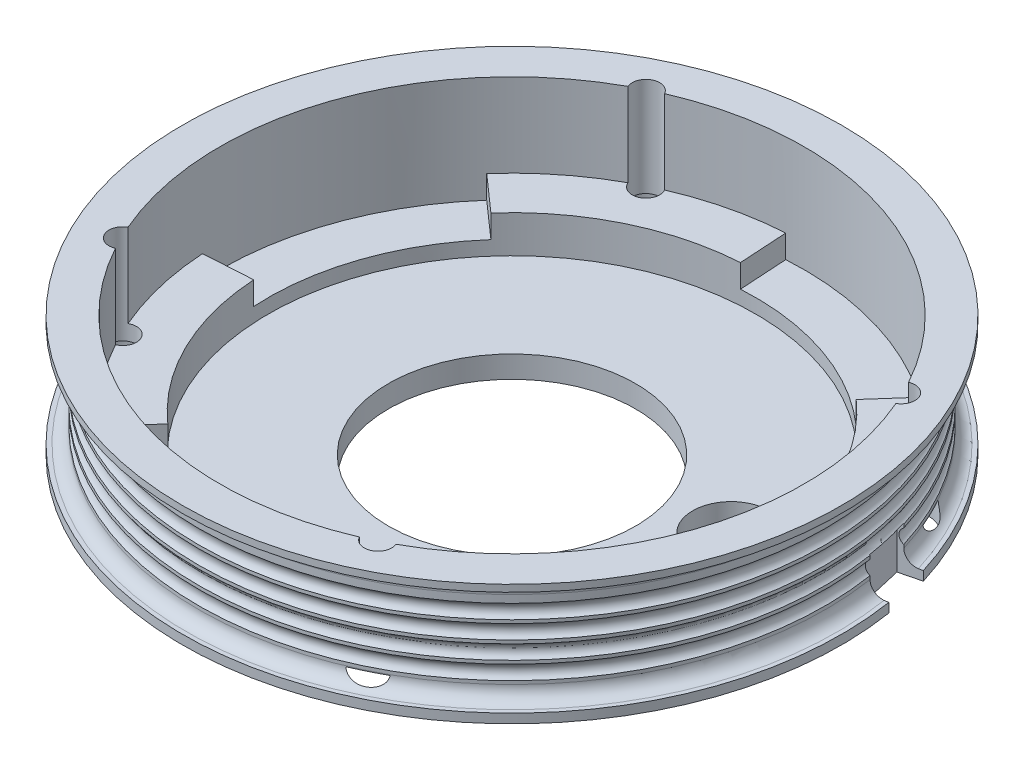
SolidWorks part; units mm, degrees
ref_plane "Front Plane" through (0, 0, 0) normal (0, 0, 1) x (1, 0, 0)
ref_plane "Top Plane" through (0, 0, 0) normal (0, 1, 0) x (1, 0, 0)
ref_plane "Right Plane" through (0, 0, 0) normal (1, 0, 0) x (0, 0, -1)
sketch "Sketch1" plane through (0, 0, 0) normal (0, 1, 0) x (1, 0, 0)
  circle A1 centre (0, 0) radius 23
extrude "Boss-Extrude1" add sketch "Sketch1" against normal blind 2
sketch "Sketch2" plane through (0, 0, 0) normal (0, 1, 0) x (1, 0, 0)
  circle A0 centre (0, 0) radius 30
  circle A1 centre (0, 0) radius 22.2
extrude "Boss-Extrude2" add sketch "Sketch2" along normal blind 11
sketch "Sketch3" plane through (0, 0, 0) normal (0, 1, 0) x (1, 0, 0)
  circle A0 centre (0, 0) radius 11.25
extrude "Cut-Extrude1" cut sketch "Sketch3" against normal blind 10 contours A0
ref_plane "Plane1" through (0, 11, 0) normal (0, 1, 0) x (1, 0, 0)
ref_plane "Plane2" through (0, -2, 0) normal (0, -1, 0) x (-1, 0, 0)
ref_plane "Plane3" through (0, 0, 0) normal (0, -1, 0) x (-1, 0, 0)
sketch "Sketch6" plane through (0, 0, 0) normal (1, 0, 0) x (0, 0, -1)
  line L0 (29.6174, 10.3701) -> (30.176, 10.3701)
  line L1 (30.176, 10.3701) -> (30.176, 0.8441)
  line L2 (30.176, 5.6071) -> (35.5665, 5.6071) construction
  line L3 (30.176, 0.8441) -> (29.6174, 0.8441)
  line L4 (28.5358, 8.7702) -> (28.5358, 8.4631)
  line L5 (28.5358, 7.1702) -> (28.5358, 6.8631)
  line L6 (28.5358, 5.5702) -> (28.5358, 5.2631)
  line L7 (28.5358, 3.9702) -> (28.5358, 3.6631)
  line L8 (28.5358, 2.3702) -> (28.5358, 2.0631)
  line L9 (28.5358, 9.1511) -> (28.5358, 8.7702)
  arc A0 (28.5358, 9.1511) -> (29.6174, 10.3701) centre (29.7636, 9.1511) cw
  arc A1 (28.5358, 8.4631) -> (28.5358, 7.1702) centre (28.9161, 7.8166) ccw
  arc A2 (28.5358, 6.8631) -> (28.5358, 5.5702) centre (28.9161, 6.2166) ccw
  arc A3 (28.5358, 5.2631) -> (28.5358, 3.9702) centre (28.9161, 4.6166) ccw
  arc A4 (28.5358, 3.6631) -> (28.5358, 2.3702) centre (28.9161, 3.0166) ccw
  arc A5 (28.5358, 2.0631) -> (29.6174, 0.8441) centre (29.7636, 2.0631) ccw
  dimension "D2" = 1.6
  dimension "D3" = 1.6
  dimension "D4" = 1.6
ref_axis "Axis1" through (0, -2, 0) along (0, 1, 0)
sketch "Sketch10" plane through (0, 11, 0) normal (0, 1, 0) x (1, 0, 0)
  line L0 (8.2003, -23.949) -> (8.0956, -20.7964)
  line L1 (8.2003, -23.949) -> (7.2077, -21.0502) construction
  line L2 (8.2003, -23.949) -> (6.3506, -21.3939)
  line L3 (6.1946, -24.5444) -> (6.3506, -21.3939)
  line L5 (6.1946, -24.5444) -> (4.5623, -21.8453)
  line L6 (4.1466, -24.9721) -> (4.5623, -21.8453)
  line L7 (4.1466, -24.9721) -> (2.7427, -22.1474)
  line L8 (2.0703, -25.2292) -> (2.7427, -22.1474)
  line L9 (2.0703, -25.2292) -> (0.9044, -22.2983)
  line L10 (-0.0202, -25.314) -> (0.9044, -22.2983)
  line L11 (-0.0202, -25.314) -> (-0.9401, -22.2968)
  line L12 (-2.1106, -25.2259) -> (-0.9401, -22.2968)
  line L13 (-2.1106, -25.2259) -> (-2.7781, -22.143)
  line L14 (-4.1865, -24.9654) -> (-2.7781, -22.143)
  line L15 (-4.1865, -24.9654) -> (-4.5972, -21.838)
  line L16 (-6.2338, -24.5345) -> (-4.5972, -21.838)
  line L17 (-6.2338, -24.5345) -> (-6.3848, -21.3837)
  line L18 (-8.2386, -23.9359) -> (-6.3848, -21.3837)
  line L19 (-8.2386, -23.9359) -> (-8.1289, -20.7835)
  line L20 (-10.1871, -23.1738) -> (-8.1289, -20.7835)
  line L21 (-10.1871, -23.1738) -> (-9.8174, -20.0412)
  line L22 (-12.0659, -22.2534) -> (-9.8174, -20.0412)
  line L23 (-12.0659, -22.2534) -> (-11.4389, -19.162)
  line L24 (-13.8624, -21.181) -> (-11.4389, -19.162)
  line L25 (-13.8624, -21.181) -> (-12.9822, -18.152)
  line L26 (-15.5642, -19.9639) -> (-12.9822, -18.152)
  line L27 (-15.5642, -19.9639) -> (-14.4368, -17.0179)
  line L28 (-17.1596, -18.6104) -> (-14.4368, -17.0179)
  line L29 (-17.1596, -18.6104) -> (-15.7928, -15.7676)
  line L30 (-18.6378, -17.1298) -> (-15.7928, -15.7676)
  line L31 (-18.6378, -17.1298) -> (-17.041, -14.4096)
  line L32 (-19.9887, -15.5322) -> (-17.041, -14.4096)
  line L33 (-19.9887, -15.5322) -> (-18.1727, -12.9531)
  line L34 (-21.2031, -13.8285) -> (-18.1727, -12.9531)
  line L35 (-21.2031, -13.8285) -> (-19.1803, -11.4082)
  line L36 (-22.2726, -12.0304) -> (-19.1803, -11.4082)
  line L37 (-22.2726, -12.0304) -> (-20.0569, -9.7854)
  line L38 (-23.19, -10.15) -> (-20.0569, -9.7854)
  line L39 (-23.19, -10.15) -> (-20.7964, -8.0956)
  line L40 (-23.949, -8.2003) -> (-20.7964, -8.0956)
  line L41 (-23.949, -8.2003) -> (-21.3939, -6.3506)
  line L42 (-24.5444, -6.1946) -> (-21.3939, -6.3506)
  line L43 (-24.5444, -6.1946) -> (-21.8453, -4.5623)
  line L44 (-24.9721, -4.1466) -> (-21.8453, -4.5623)
  line L45 (-24.9721, -4.1466) -> (-22.1474, -2.7427)
  line L46 (-25.2292, -2.0703) -> (-22.1474, -2.7427)
  line L47 (-25.2292, -2.0703) -> (-22.2983, -0.9044)
  line L48 (-25.314, 0.0202) -> (-22.2983, -0.9044)
  line L49 (-25.314, 0.0202) -> (-22.2968, 0.9401)
  line L50 (-25.2259, 2.1106) -> (-22.2968, 0.9401)
  line L51 (-25.2259, 2.1106) -> (-22.143, 2.7781)
  line L52 (-24.9654, 4.1865) -> (-22.143, 2.7781)
  line L53 (-24.9654, 4.1865) -> (-21.838, 4.5972)
  line L54 (-24.5345, 6.2338) -> (-21.838, 4.5972)
  line L55 (-24.5345, 6.2338) -> (-21.3837, 6.3848)
  line L56 (-23.9359, 8.2386) -> (-21.3837, 6.3848)
  line L57 (-23.9359, 8.2386) -> (-20.7835, 8.1289)
  line L58 (-23.1738, 10.1871) -> (-20.7835, 8.1289)
  line L59 (-23.1738, 10.1871) -> (-20.0412, 9.8174)
  line L60 (-22.2534, 12.0659) -> (-20.0412, 9.8174)
  line L61 (-22.2534, 12.0659) -> (-19.162, 11.4389)
  line L62 (-21.181, 13.8624) -> (-19.162, 11.4389)
  line L63 (-21.181, 13.8624) -> (-18.152, 12.9822)
  line L64 (-19.9639, 15.5642) -> (-18.152, 12.9822)
  line L65 (-19.9639, 15.5642) -> (-17.0179, 14.4368)
  line L66 (-18.6104, 17.1596) -> (-17.0179, 14.4368)
  line L67 (-18.6104, 17.1596) -> (-15.7676, 15.7928)
  line L68 (-17.1298, 18.6378) -> (-15.7676, 15.7928)
  line L69 (-17.1298, 18.6378) -> (-14.4096, 17.041)
  line L70 (-15.5322, 19.9887) -> (-14.4096, 17.041)
  line L71 (-15.5322, 19.9887) -> (-12.9531, 18.1727)
  line L72 (-13.8285, 21.2031) -> (-12.9531, 18.1727)
  line L73 (-13.8285, 21.2031) -> (-11.4082, 19.1803)
  line L74 (-12.0304, 22.2726) -> (-11.4082, 19.1803)
  line L75 (-12.0304, 22.2726) -> (-9.7854, 20.0569)
  line L76 (-10.15, 23.19) -> (-9.7854, 20.0569)
  line L77 (-10.15, 23.19) -> (-8.0956, 20.7964)
  line L78 (-8.2003, 23.949) -> (-8.0956, 20.7964)
  line L79 (-8.2003, 23.949) -> (-6.3506, 21.3939)
  line L80 (-6.1946, 24.5444) -> (-6.3506, 21.3939)
  line L81 (-6.1946, 24.5444) -> (-4.5623, 21.8453)
  line L82 (-4.1466, 24.9721) -> (-4.5623, 21.8453)
  line L83 (-4.1466, 24.9721) -> (-2.7427, 22.1474)
  line L84 (-2.0703, 25.2292) -> (-2.7427, 22.1474)
  line L85 (-2.0703, 25.2292) -> (-0.9044, 22.2983)
  line L86 (0.0202, 25.314) -> (-0.9044, 22.2983)
  line L87 (0.0202, 25.314) -> (0.9401, 22.2968)
  line L88 (2.1106, 25.2259) -> (0.9401, 22.2968)
  line L89 (2.1106, 25.2259) -> (2.7781, 22.143)
  line L90 (4.1865, 24.9654) -> (2.7781, 22.143)
  line L91 (4.1865, 24.9654) -> (4.5972, 21.838)
  line L92 (6.2338, 24.5345) -> (4.5972, 21.838)
  line L93 (6.2338, 24.5345) -> (6.3848, 21.3837)
  line L94 (8.2386, 23.9359) -> (6.3848, 21.3837)
  line L95 (8.2386, 23.9359) -> (8.1289, 20.7835)
  line L96 (10.1871, 23.1738) -> (8.1289, 20.7835)
  line L97 (10.1871, 23.1738) -> (9.8174, 20.0412)
  line L98 (12.0659, 22.2534) -> (9.8174, 20.0412)
  line L99 (12.0659, 22.2534) -> (11.4389, 19.162)
  line L100 (13.8624, 21.181) -> (11.4389, 19.162)
  line L101 (13.8624, 21.181) -> (12.9822, 18.152)
  line L102 (15.5642, 19.9639) -> (12.9822, 18.152)
  line L103 (15.5642, 19.9639) -> (14.4368, 17.0179)
  line L104 (17.1596, 18.6104) -> (14.4368, 17.0179)
  line L105 (17.1596, 18.6104) -> (15.7928, 15.7676)
  line L106 (18.6378, 17.1298) -> (15.7928, 15.7676)
  line L107 (18.6378, 17.1298) -> (17.041, 14.4096)
  line L108 (19.9887, 15.5322) -> (17.041, 14.4096)
  line L109 (19.9887, 15.5322) -> (18.1727, 12.9531)
  line L110 (21.2031, 13.8285) -> (18.1727, 12.9531)
  line L111 (21.2031, 13.8285) -> (19.1803, 11.4082)
  line L112 (22.2726, 12.0304) -> (19.1803, 11.4082)
  line L113 (22.2726, 12.0304) -> (20.0569, 9.7854)
  line L114 (23.19, 10.15) -> (20.0569, 9.7854)
  line L115 (23.19, 10.15) -> (20.7964, 8.0956)
  line L116 (23.949, 8.2003) -> (20.7964, 8.0956)
  line L117 (23.949, 8.2003) -> (21.3939, 6.3506)
  line L118 (24.5444, 6.1946) -> (21.3939, 6.3506)
  line L119 (24.5444, 6.1946) -> (21.8453, 4.5623)
  line L120 (24.9721, 4.1466) -> (21.8453, 4.5623)
  line L121 (24.9721, 4.1466) -> (22.1474, 2.7427)
  line L122 (25.2292, 2.0703) -> (22.1474, 2.7427)
  line L123 (25.2292, 2.0703) -> (22.2983, 0.9044)
  line L124 (25.314, -0.0202) -> (22.2983, 0.9044)
  line L125 (25.314, -0.0202) -> (22.2968, -0.9401)
  line L126 (25.2259, -2.1106) -> (22.2968, -0.9401)
  line L127 (25.2259, -2.1106) -> (22.143, -2.7781)
  line L128 (24.9654, -4.1865) -> (22.143, -2.7781)
  line L129 (24.9654, -4.1865) -> (21.838, -4.5972)
  line L130 (24.5345, -6.2338) -> (21.838, -4.5972)
  line L131 (24.5345, -6.2338) -> (21.3837, -6.3848)
  line L132 (23.9359, -8.2386) -> (21.3837, -6.3848)
  line L133 (23.9359, -8.2386) -> (20.7835, -8.1289)
  line L134 (23.1738, -10.1871) -> (20.7835, -8.1289)
  line L135 (23.1738, -10.1871) -> (20.0412, -9.8174)
  line L136 (22.2534, -12.0659) -> (20.0412, -9.8174)
  line L137 (22.2534, -12.0659) -> (19.162, -11.4389)
  line L138 (21.181, -13.8624) -> (19.162, -11.4389)
  line L139 (21.181, -13.8624) -> (18.152, -12.9822)
  line L140 (19.9639, -15.5642) -> (18.152, -12.9822)
  line L141 (19.9639, -15.5642) -> (17.0179, -14.4368)
  line L142 (18.6104, -17.1596) -> (17.0179, -14.4368)
  line L143 (18.6104, -17.1596) -> (15.7676, -15.7928)
  line L144 (17.1298, -18.6378) -> (15.7676, -15.7928)
  line L145 (17.1298, -18.6378) -> (14.4096, -17.041)
  line L146 (15.5322, -19.9887) -> (14.4096, -17.041)
  line L147 (15.5322, -19.9887) -> (12.9531, -18.1727)
  line L148 (13.8285, -21.2031) -> (12.9531, -18.1727)
  line L149 (13.8285, -21.2031) -> (11.4082, -19.1803)
  line L150 (12.0304, -22.2726) -> (11.4082, -19.1803)
  line L151 (12.0304, -22.2726) -> (9.7854, -20.0569)
  line L152 (10.15, -23.19) -> (9.7854, -20.0569)
  line L153 (10.15, -23.19) -> (8.0956, -20.7964)
  line L184 (7.2077, -21.0502) -> (8.5243, -24.8951) construction
  point P235 (0, 0)
  dimension "D1" = 17
extrude "Cut-Extrude8" cut sketch "Sketch10" against normal blind 5.5
sketch "Sketch5" plane through (0, 11, 0) normal (0, 1, 0) x (1, 0, 0)
  line L0 (0, 0) -> (20.0775, 9.7954) construction
  line L1 (20.0775, 9.7954) -> (26.9622, 13.1544) construction
  circle A1 centre (0, 0) radius 30 construction
  circle A2 centre (23.8167, 11.6197) radius 1.25
  circle A3 centre (11.6197, -23.8167) radius 1.25
  circle A5 centre (-23.8167, -11.6197) radius 1.25
  circle A7 centre (-11.6197, 23.8167) radius 1.25
  point P21 (0, 0)
  dimension "D1" = 4
extrude "Cut-Extrude3" cut sketch "Sketch5" against normal through all
sketch "Sketch8" plane through (0, 0, 0) normal (0, -1, 0) x (-1, 0, 0)
  circle A0 centre (-23.8167, 11.6197) radius 2.5
  circle A1 centre (11.6197, 23.8167) radius 2.5
  circle A2 centre (23.8167, -11.6197) radius 2.5
  circle A3 centre (-11.6197, -23.8167) radius 2.5
  point P11 (0, 0)
extrude "Cut-Extrude5" cut sketch "Sketch8" against normal blind 2
ref_plane "Plane4" through (0, 0, 0) normal (0, 1, 0) x (1, 0, 0)
revolve "Cut-Revolve1" cut sketch "Sketch6" angle 360 about axis through (0, -2, 0) along (0, 1, 0)
sketch "Sketch12" plane through (0, -2, 0) normal (0, -1, 0) x (-1, 0, 0)
  line L2 (-19.6103, 3.4061) -> (-22.6044, 3.9868)
  line L3 (-19.1966, 5.5081) -> (-22.0729, 6.2962)
  line L8 (-22.7811, -2.8065) -> (-13.2828, -1.9137)
  line L9 (-19.2445, 12.5101) -> (-11.1512, 7.8264)
  line L11 (-13.2828, -1.9137) -> (-11.1512, 7.8264)
  arc A0 (-19.2445, 12.5101) -> (-22.0729, 6.2962) centre (0, 0) ccw
  arc A1 (-22.6044, 3.9868) -> (-22.7811, -2.8065) centre (0, 0) ccw
  arc A10 (-19.6103, 3.4061) -> (-19.1966, 5.5081) centre (-16.1341, 3.8136) ccw
extrude "Boss-Extrude3" add sketch "Sketch12" along normal blind 3 contours A10 A0 L8 L11 L9 region at (12.5103, -2, -3.1003)
sketch "Sketch13" plane through (0, -2, 0) normal (0, -1, 0) x (-1, 0, 0)
  circle A0 centre (-16.1341, 3.8136) radius 3.5
extrude "Cut-Extrude9" cut sketch "Sketch13" against normal blind 3 contours A0
ref_plane "Plane5" through (0, 0, 0) normal (0, -1, 0) x (-1, 0, 0)
sketch "Sketch15" plane through (0, 0, 0) normal (0, -1, 0) x (-1, 0, 0)
  line L0 (-27.6851, 4.3056) -> (-29.0627, 4.5727)
  line L1 (-26.7661, 8.2772) -> (-28.1306, 8.6203)
  line L2 (-29.0627, 4.5727) -> (-29.8955, 4.7341)
  line L3 (-28.1306, 8.6203) -> (-29.0951, 8.8628)
  line L4 (-29.0951, 8.8628) -> (-29.8955, 4.7341)
  line L5 (-27.6851, 4.3056) -> (-26.7661, 8.2772)
extrude "Cut-Extrude10" cut sketch "Sketch15" against normal blind 4
sketch "Sketch16" plane through (0, 5.5, 0) normal (0, 1, 0) x (1, 0, 0)
  circle A0 centre (0, 0) radius 26.6
extrude "Cut-Extrude11" cut sketch "Sketch16" against normal blind 2.1 and the other way blind 10
sketch "Sketch17" plane through (0, 3.4, 0) normal (0, 1, 0) x (1, 0, 0)
  line L0 (-19.9521, -9.7342) -> (23.8167, 11.6197) construction
  line L1 (-11.6197, 23.8167) -> (11.6197, -23.8167) construction
  line L2 (-1.6271, 26.5502) -> (-1.3579, 22.1584)
  line L3 (-19.9243, 17.6233) -> (-16.6286, 14.7082)
  line L4 (17.6233, 19.9243) -> (14.7082, 16.6286)
  line L5 (26.5502, 1.6271) -> (22.1584, 1.3579)
  line L6 (16.6286, -14.7082) -> (19.9243, -17.6233)
  line L7 (-22.1584, -1.3579) -> (-26.5502, -1.6271)
  line L8 (-14.7082, -16.6286) -> (-17.6233, -19.9243)
  line L9 (1.3579, -22.1584) -> (1.6271, -26.5502)
  arc A0 (-14.7082, -16.6286) -> (1.3579, -22.1584) centre (0, 0) ccw
  arc A1 (-17.6233, -19.9243) -> (1.6271, -26.5502) centre (0, 0) ccw
  arc A2 (-19.9243, 17.6233) -> (-26.5502, -1.6271) centre (0, 0) ccw
  arc A3 (-16.6286, 14.7082) -> (-22.1584, -1.3579) centre (0, 0) ccw
  arc A4 (17.6233, 19.9243) -> (-1.6271, 26.5502) centre (0, 0) ccw
  arc A5 (14.7082, 16.6286) -> (-1.3579, 22.1584) centre (0, 0) ccw
  arc A6 (16.6286, -14.7082) -> (22.1584, 1.3579) centre (0, 0) ccw
  arc A7 (19.9243, -17.6233) -> (26.5502, 1.6271) centre (0, 0) ccw
  circle M5 centre (0, 0) radius 22.2
  dimension "D1" = 22.5
  dimension "D2" = 22.5
extrude "Cut-Extrude12" cut sketch "Sketch17" against normal blind 2.1 contours L3 A1 L7 M5 | L4 A1 L2 M5 | L6 A1 L5 M5 | L8 A1 L9 M5 region at (7.7595, 3.4, -22.5441) region at (-22.5441, 3.4, -7.7595) region at (22.5441, 3.4, 7.7595) region at (-7.7595, 3.4, 22.5441)
